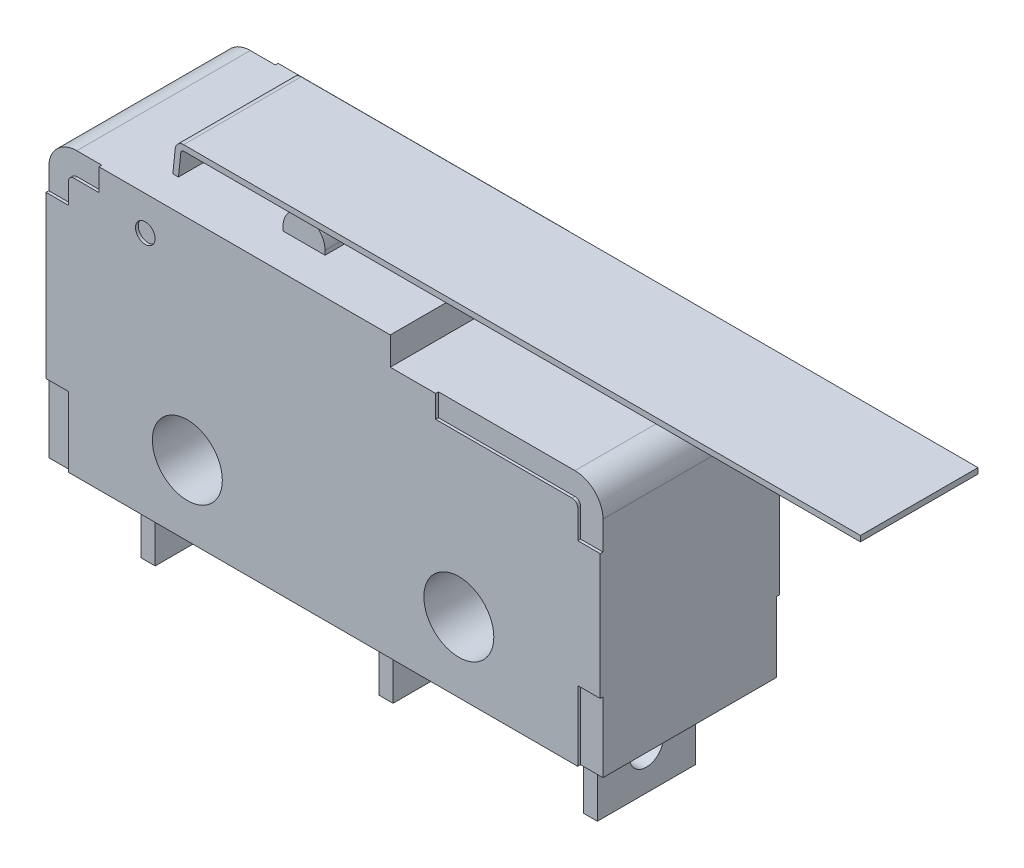
SolidWorks part; units mm, degrees
ref_plane "Front Plane" through (0, 0, 0) normal (0, 0, 1) x (1, 0, 0)
ref_plane "Top Plane" through (0, 0, 0) normal (0, 1, 0) x (1, 0, 0)
ref_plane "Right Plane" through (0, 0, 0) normal (1, 0, 0) x (0, 0, -1)
sketch "Sketch1" plane through (0, 0, 0) normal (0, 0, 1) x (1, 0, 0)
  line L1 (-9.9, 7.5) -> (2.4, 7.5)
  line L2 (-9.9, 7.5) -> (-9.9, -2.5)
  line L3 (-9.9, -2.5) -> (9.9, -2.5)
  line L4 (9.9, 6.5) -> (9.9, -2.5)
  line L6 (2.4, 7.5) -> (2.4, 6.5)
  line L7 (2.4, 6.5) -> (9.9, 6.5)
  circle A0 centre (-4.85, 0) radius 1.25
  circle A1 centre (4.85, 0) radius 1.25
  dimension "D4" = 2.5
  dimension "D1" = 10
  dimension "D2" = 19.8
  dimension "D3" = 9.7
  dimension "D5" = 7.5
  dimension "D6" = 4.85
  dimension "D7" = 1
  dimension "D8" = 7.5
  dimension "D9" = 9.9
extrude "Extrude1" add sketch "Sketch1" along normal blind 3.2 and the other way blind 3.2
fillet "Fillet1" radius 1 2 edges at (-9.9, 7.5, 0) (9.9, 6.5, 0)
sketch "Sketch2" plane through (0, 0, 3.2) normal (0, 0, 1) x (1, 0, 0)
  line L0 (8.9, 6.5) -> (2.4, 6.5) construction
  line L1 (9.9, -2.5) -> (9.9, 5.5) construction
  line L2 (-9.9, -2.5) -> (9.9, -2.5) construction
  line L3 (2.4, 7.5) -> (-8.9, 7.5) construction
  line L4 (-9.9, 6.5) -> (-9.9, -2.5) construction
  line L5 (8.9, 6.5) -> (4.0242, 6.5)
  line L6 (9.9, -2.5) -> (9.9, 0)
  line L7 (-9.9, -2.5) -> (-9.1, -2.5)
  line L8 (-8.0064, 7.5) -> (-8.9, 7.5)
  line L9 (-9.9, 6.5) -> (-9.9, 5.7619)
  line L10 (-8.0064, 6.7) -> (-8.9, 6.7)
  line L11 (-9.1, 6.5) -> (-9.1, 5.7619)
  line L12 (9.1, -2.5) -> (9.9, -2.5)
  line L13 (9.1, -1.7) -> (9.1, 0)
  line L14 (8.9, 5.7) -> (4.0242, 5.7)
  line L15 (-8.0064, 7.5) -> (-8.0064, 6.7)
  line L16 (-9.9, 5.7619) -> (-9.1, 5.7619)
  line L17 (-9.1, -1.7) -> (-9.1, -2.5)
  line L18 (-9.9, 0) -> (-9.1, 0)
  line L19 (-9.1, 0) -> (-9.1, -1.7)
  line L20 (-9.1, 6.5) -> (-9.1, -1.7) construction
  line L21 (2.4, 6.7) -> (-8.9, 6.7) construction
  line L22 (2.4, 7.5) -> (-8.9, 7.5) construction
  line L23 (-9.9, 0) -> (-9.9, -2.5)
  line L24 (-9.9, 6.5) -> (-9.9, -2.5) construction
  line L25 (9.1, 0) -> (9.9, 0)
  line L26 (9.1, -1.7) -> (9.1, -2.5)
  line L27 (-9.9, -2.5) -> (9.9, -2.5) construction
  line L28 (-9.1, -1.7) -> (9.1, -1.7) construction
  line L29 (4.0242, 6.5) -> (4.0242, 5.7)
  line L30 (8.9, 5.7) -> (2.4, 5.7) construction
  line L31 (8.9, 6.5) -> (2.4, 6.5) construction
  line L32 (9.1, 4.4827) -> (9.9, 4.4827)
  line L33 (9.1, 4.4827) -> (9.1, 5.5)
  line L34 (9.1, -1.7) -> (9.1, 5.5) construction
  line L35 (9.9, 4.4827) -> (9.9, 5.5)
  line L36 (9.9, -2.5) -> (9.9, 5.5) construction
  arc A0 (9.9, 5.5) -> (8.9, 6.5) centre (8.9, 5.5) ccw construction
  arc A1 (-8.9, 7.5) -> (-9.9, 6.5) centre (-8.9, 6.5) ccw construction
  arc A2 (9.9, 5.5) -> (8.9, 6.5) centre (8.9, 5.5) ccw
  arc A3 (-8.9, 7.5) -> (-9.9, 6.5) centre (-8.9, 6.5) ccw
  arc A4 (-8.9, 6.7) -> (-9.1, 6.5) centre (-8.9, 6.5) ccw
  arc A5 (9.1, 5.5) -> (8.9, 5.7) centre (8.9, 5.5) ccw
  dimension "D1" = 0.8
extrude "Cut-Extrude1" cut sketch "Sketch2" against normal blind 0.1
sketch "Sketch3" plane through (0, 0, -3.2) normal (0, 0, -1) x (-1, 0, 0)
  line L5 (9.1, -1.7) -> (9.1, -2.5)
  line L6 (8.9, 7.5) -> (8.0064, 7.5)
  line L7 (9.9, 5.7619) -> (9.9, 6.5)
  line L8 (9.1, 5.7619) -> (9.9, 5.7619)
  line L9 (9.1, 6.5) -> (9.1, 5.7619)
  line L10 (8.0064, 6.7) -> (8.9, 6.7)
  line L11 (8.0064, 7.5) -> (8.0064, 6.7)
  line L12 (8.9, 7.5) -> (8.0064, 7.5)
  line L13 (9.9, 5.7619) -> (9.9, 6.5)
  line L14 (9.1, 5.7619) -> (9.9, 5.7619)
  line L15 (9.1, 6.5) -> (9.1, 5.7619)
  line L16 (8.0064, 6.7) -> (8.9, 6.7)
  line L17 (8.0064, 7.5) -> (8.0064, 6.7)
  line L18 (9.1, 0) -> (9.1, -1.7)
  line L19 (9.9, 0) -> (9.1, 0)
  line L20 (9.9, -2.5) -> (9.9, 0)
  line L21 (9.1, -2.5) -> (9.9, -2.5)
  line L22 (9.1, -1.7) -> (9.1, -2.5)
  line L23 (9.1, 0) -> (9.1, -1.7)
  line L24 (9.9, 0) -> (9.1, 0)
  line L25 (9.9, -2.5) -> (9.9, 0)
  line L26 (9.1, -2.5) -> (9.9, -2.5)
  line L27 (-9.9, 0) -> (-9.9, -2.5)
  line L28 (-9.9, -2.5) -> (-9.1, -2.5)
  line L29 (-9.1, -2.5) -> (-9.1, -1.7)
  line L30 (-9.1, -1.7) -> (-9.1, 0)
  line L31 (-9.1, 0) -> (-9.9, 0)
  line L32 (-9.9, 0) -> (-9.9, -2.5)
  line L33 (-9.9, -2.5) -> (-9.1, -2.5)
  line L34 (-9.1, -2.5) -> (-9.1, -1.7)
  line L35 (-9.1, -1.7) -> (-9.1, 0)
  line L36 (-9.1, 0) -> (-9.9, 0)
  line L38 (-4.0242, 5.7) -> (-4.0242, 6.5)
  line L39 (-4.0242, 6.5) -> (-8.9, 6.5)
  line L40 (-9.9, 5.5) -> (-9.9, 4.4827)
  line L41 (-9.9, 4.4827) -> (-9.1, 4.4827)
  line L42 (-9.1, 4.4827) -> (-9.1, 5.5)
  line L43 (-8.9, 5.7) -> (-4.0242, 5.7)
  line L44 (-4.0242, 5.7) -> (-4.0242, 6.5)
  line L45 (-4.0242, 6.5) -> (-8.9, 6.5)
  line L46 (-9.9, 5.5) -> (-9.9, 4.4827)
  line L47 (-9.9, 4.4827) -> (-9.1, 4.4827)
  line L48 (-9.1, 4.4827) -> (-9.1, 5.5)
  line L49 (-8.9, 5.7) -> (-4.0242, 5.7)
  arc A2 (9.9, 6.5) -> (8.9, 7.5) centre (8.9, 6.5) ccw
  arc A3 (9.1, 6.5) -> (8.9, 6.7) centre (8.9, 6.5) ccw
  arc A4 (9.9, 6.5) -> (8.9, 7.5) centre (8.9, 6.5) ccw
  arc A5 (9.1, 6.5) -> (8.9, 6.7) centre (8.9, 6.5) ccw
  arc A6 (-8.9, 6.5) -> (-9.9, 5.5) centre (-8.9, 5.5) ccw
  arc A7 (-8.9, 5.7) -> (-9.1, 5.5) centre (-8.9, 5.5) ccw
  arc A8 (-8.9, 6.5) -> (-9.9, 5.5) centre (-8.9, 5.5) ccw
  arc A9 (-8.9, 5.7) -> (-9.1, 5.5) centre (-8.9, 5.5) ccw
  dimension "D1" = 0
  dimension "D2" = 0
  dimension "D3" = 0
  dimension "D4" = 0
extrude "Cut-Extrude2" cut sketch "Sketch3" against normal blind 0.1
sketch "Sketch5" plane through (0, 0, 0) normal (0, 0, 1) x (1, 0, 0)
  line L0 (-9.1, -2.5) -> (9.1, -2.5) construction
  line L1 (-7.95, -2.5) -> (-7.7, -2.5)
  line L2 (-7.95, -2.5) -> (-7.95, -5.3)
  line L3 (-7.95, -5.3) -> (-7.45, -5.3)
  line L4 (-7.45, -2.5) -> (-7.45, -5.3)
  line L5 (8.1, -2.5) -> (8.35, -2.5)
  line L6 (0.55, -2.5) -> (0.8, -2.5)
  line L7 (0.55, -2.5) -> (0.55, -5.3)
  line L8 (0.55, -5.3) -> (1.05, -5.3)
  line L9 (1.05, -2.5) -> (1.05, -5.3)
  line L10 (7.85, -2.5) -> (8.1, -2.5)
  line L11 (7.85, -2.5) -> (7.85, -5.3)
  line L12 (7.85, -5.3) -> (8.35, -5.3)
  line L13 (8.35, -2.5) -> (8.35, -5.3)
  line L14 (0.8, -2.5) -> (1.05, -2.5)
  line L15 (-7.7, -2.5) -> (-7.45, -2.5)
  dimension "D1" = 0.5
  dimension "D2" = 2.8
  dimension "D3" = 0.25
  dimension "D4" = 1.8
  dimension "D5" = 7.3
  dimension "D6" = 8.5
extrude "Extrude3" add sketch "Sketch5" along normal blind 1.75 and the other way blind 1.75
sketch "Sketch6" plane through (0, 0, 0) normal (1, 0, 0) x (0, 0, -1)
  circle A0 centre (0, -3.9) radius 0.6
extrude "Cut-Extrude3" cut sketch "Sketch6" against normal through all and the other way through all
sketch "Sketch8" plane through (0, 0, 3.2) normal (0, 0, 1) x (1, 0, 0)
  circle A0 centre (-6.352, 6.2743) radius 0.35
extrude "Cut-Extrude4" cut sketch "Sketch8" against normal blind 0.1
sketch "Sketch9" plane through (0, 0, -3.2) normal (0, 0, -1) x (-1, 0, 0)
  circle A1 centre (6.352, 6.2743) radius 0.35
  circle A2 centre (6.352, 6.2743) radius 0.35
  dimension "D1" = 0
extrude "Cut-Extrude5" cut sketch "Sketch9" against normal blind 0.1
sketch "Sketch10" plane through (0, 0, 0) normal (0, 0, 1) x (1, 0, 0)
  line L4 (-6.3684, 7.5) -> (-6.2639, 8.4945)
  line L5 (-6.2639, 8.4945) -> (11.4361, 8.4945)
  line L6 (11.4361, 8.4945) -> (12.6827, 3.4945)
  line L7 (12.6827, 3.4945) -> (19.6444, 2.7628)
  dimension "D1" = 17.7
  dimension "D2" = 1
  dimension "D3" = 5
  dimension "D4" = 110
  dimension "D5" = 104
  dimension "D6" = 7
  dimension "D7" = 96
sketch "Sketch11" plane through (0, 0, 0) normal (0, 0, 1) x (1, 0, 0)
  line L6 (-2.73, 7.65) -> (-2.73, 6.9)
  line L7 (-2.73, 6.9) -> (-1.23, 6.9)
  line L8 (-1.23, 6.9) -> (-1.23, 7.65)
  arc A2 (-1.23, 7.65) -> (-2.73, 7.65) centre (-1.98, 7.65) ccw
extrude "Extrude4" add sketch "Sketch11" along normal blind 1.9 and the other way blind 1.9
sketch "Sketch12" plane through (0, 0, 0) normal (0, 0, 1) x (1, 0, 0)
  line L0 (-6.3684, 7.5) -> (-6.2639, 8.4945) construction
  line L4 (-6.3684, 7.5) -> (-6.2639, 8.4945)
  line L5 (-6.2639, 8.4945) -> (18.1, 8.4945)
  line L7 (-9.9, 5.7619) -> (-9.9, 0) construction
  dimension "D1" = 28
extrude "Extrude-Thin3" add sketch "Sketch12" along normal blind 2.1 and the other way blind 2.1 thin thin type two direction wall 0.1 second wall 0.1
fillet "Fillet6" radius 0.1 1 edges at (-6.1739, 8.3945, 0)
fillet "Fillet7" radius 0.3 1 edges at (-6.3539, 8.5945, 0)
ref_plane "Board Surface" through (0, -2.5, 0) normal (0, 1, 0) x (-1, 0, 0)
sketch "Component_Outline" plane through (0, -2.5, 0) normal (0, 1, 0) x (-1, 0, 0)
  line L0 (9.9, 3.2) -> (9.9, -3.2)
  line L1 (9.9, -3.2) -> (-9.9, -3.2)
  line L2 (-9.9, -3.2) -> (-9.9, -2.1)
  line L3 (6.0838, -2.1) -> (-18.1, -2.1) construction
  line L4 (-9.9, 3.1) -> (-9.9, -3.1) construction
  line L5 (-9.9, -2.1) -> (-18.1, -2.1)
  line L6 (-18.1, -2.1) -> (-18.1, 2.1)
  line L7 (-18.1, 2.1) -> (-9.9, 2.1)
  line L8 (6.0838, 2.1) -> (-18.1, 2.1) construction
  line L9 (-9.9, 2.1) -> (-9.9, 3.2)
  line L10 (-9.9, 3.2) -> (9.9, 3.2)
  point P20 (0, 0)
